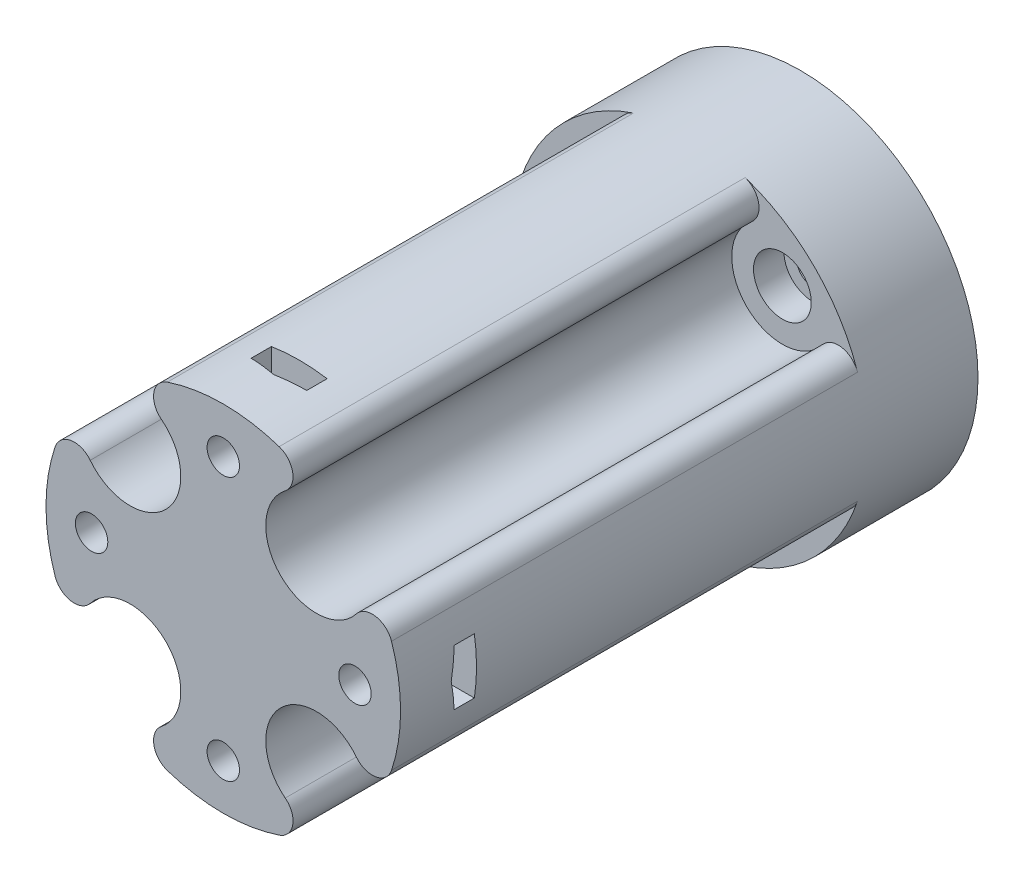
SolidWorks part; units mm, degrees
ref_plane "Front Plane" through (0, 0, 0) normal (1, 0, 0) x (0, 1, 0)
ref_plane "Top Plane" through (0, 0, 0) normal (0, 0, 1) x (0, 1, 0)
ref_plane "Right Plane" through (0, 0, 0) normal (0, 1, 0) x (-1, 0, 0)
sketch "Sketch1" plane through (0, 0, 0) normal (0, 0, 1) x (0, 1, 0)
  line L0 (0, 0) -> (9.1924, 9.1924) construction
  circle A0 centre (0, 0) radius 17.5
  circle A1 centre (0, 0) radius 13 construction
  circle A2 centre (9.1924, 9.1924) radius 1.6
  circle A3 centre (9.1924, 9.1924) radius 2.85
  circle A4 centre (9.1924, -9.1924) radius 2.85
  circle A5 centre (9.1924, -9.1924) radius 1.6
  circle A6 centre (-9.1924, -9.1924) radius 2.85
  circle A7 centre (-9.1924, -9.1924) radius 1.6
  circle A8 centre (-9.1924, 9.1924) radius 2.85
  circle A9 centre (-9.1924, 9.1924) radius 1.6
  point P19 (0, 0)
  dimension "D1" = 35
  dimension "D2" = 26
  dimension "D3" = 3.2
  dimension "D4" = 5.7
  dimension "D5" = 4
extrude "Boss-Extrude1" add sketch "Sketch1" along normal blind 57 contours A0 A8 A6 A4 A3 region at (0, 0, 0)
extrude "Boss-Extrude2" add sketch "Sketch1<3>" along normal blind 8 contours A6 A7 | A8 A9 | A4 A5 | A3 A2 region at (-9.1924, 6.423, 0) region at (9.1924, 6.423, 0) region at (9.1924, -11.9618, 0) region at (-9.1924, -11.9618, 0)
sketch "Sketch1<3>" plane through (0, 0, 0) normal (0, 0, 1) x (0, 1, 0) same geometry as "Sketch1"
sketch "Sketch2" plane through (0, 0, 57) normal (0, 0, 1) x (1, 0, 0)
  circle A0 centre (-9.1924, 9.1924) radius 5
  circle A1 centre (9.1924, 9.1924) radius 5
  circle A2 centre (9.1924, -9.1924) radius 5
  circle A3 centre (-9.1924, -9.1924) radius 5
  dimension "D1" = 10
  dimension "D2" = 2
  dimension "D3" = 2
extrude "Cut-Extrude1" cut sketch "Sketch2" against normal blind 46
fillet "Fillet1" radius 2 8 edges at (14.0286, 10.4618, 34) (-14.0286, 10.4618, 34) (-10.4618, 14.0286, 34) (10.4618, 14.0286, 34) (14.0286, -10.4618, 34) (10.4618, -14.0286, 34) (-10.4618, -14.0286, 34) (-14.0286, -10.4618, 34)
sketch "Sketch3" plane through (0, 0, 57) normal (0, 0, 1) x (1, 0, 0)
  line L0 (-2.75, 15.75) -> (-2.75, 17.2826)
  line L2 (-2.75, 15.75) -> (-2.75, 10.25)
  line L3 (-2.75, 10.25) -> (2.75, 10.25)
  line L4 (2.75, 15.75) -> (2.75, 10.25)
  line L5 (-2.75, 15.75) -> (2.75, 10.25) construction
  line L6 (-2.75, 10.25) -> (2.75, 15.75) construction
  line L7 (2.75, 15.75) -> (2.75, 17.2826)
  line L8 (15.75, -2.75) -> (10.25, -2.75)
  line L9 (10.25, 2.75) -> (10.25, -2.75)
  line L10 (15.75, 2.75) -> (10.25, 2.75)
  line L11 (15.75, 2.75) -> (17.2826, 2.75)
  line L12 (15.75, -2.75) -> (17.2826, -2.75)
  line L13 (-2.75, -15.75) -> (-2.75, -10.25)
  line L14 (2.75, -10.25) -> (-2.75, -10.25)
  line L15 (2.75, -15.75) -> (2.75, -10.25)
  line L16 (2.75, -15.75) -> (2.75, -17.2826)
  line L17 (-2.75, -15.75) -> (-2.75, -17.2826)
  line L18 (-15.75, 2.75) -> (-10.25, 2.75)
  line L19 (-10.25, -2.75) -> (-10.25, 2.75)
  line L20 (-15.75, -2.75) -> (-10.25, -2.75)
  line L21 (-15.75, -2.75) -> (-17.2826, -2.75)
  line L22 (-15.75, 2.75) -> (-17.2826, 2.75)
  circle A0 centre (0, 0) radius 13 construction
  circle A2 centre (0, 13) radius 1.6
  arc A3 (5.5152, 16.6082) -> (-5.5152, 16.6082) centre (0, 0) ccw construction
  arc A4 (-2.75, 17.2826) -> (2.75, 17.2826) centre (0, 0) cw
  arc A5 (17.2826, 2.75) -> (17.2826, -2.75) centre (0, 0) cw
  circle A6 centre (13, 0) radius 1.6
  arc A7 (2.75, -17.2826) -> (-2.75, -17.2826) centre (0, 0) cw
  circle A8 centre (0, -13) radius 1.6
  arc A9 (-17.2826, -2.75) -> (-17.2826, 2.75) centre (0, 0) cw
  circle A10 centre (-13, 0) radius 1.6
  point P41 (0, 0)
  dimension "D1" = 26
  dimension "D2" = 3.2
  dimension "D3" = 5.5
  dimension "D4" = 5.5
  dimension "D5" = 4
extrude "Cut-Extrude2" cut sketch "Sketch3" against normal blind 2.5 from offset 5 offset against normal yes
extrude "Cut-Extrude3" cut sketch "Sketch3<2>" against normal blind 10 contours A10 | A2 | A6 | A8 region at (0, 13, 57) region at (13, 0, 57) region at (0, -13, 57) region at (-13, 0, 57)
sketch "Sketch3<2>" plane through (0, 0, 57) normal (0, 0, 1) x (1, 0, 0) same geometry as "Sketch3"
chamfer "Chamfer1" distance 2.75 distance2 0.5 8 edges at (-13.7663, -2.75, 52) (-2.75, 13.7663, 52) (2.75, 13.7663, 52) (13.7663, 2.75, 52) (13.7663, -2.75, 52) (2.75, -13.7663, 52) (-2.75, -13.7663, 52) (-13.7663, 2.75, 52) first distance on face at (-14.6, 0, 52) first distance on face at (-1.6, 13, 52) first distance on face at (11.4, 0, 52) first distance on face at (-1.6, -13, 52)
